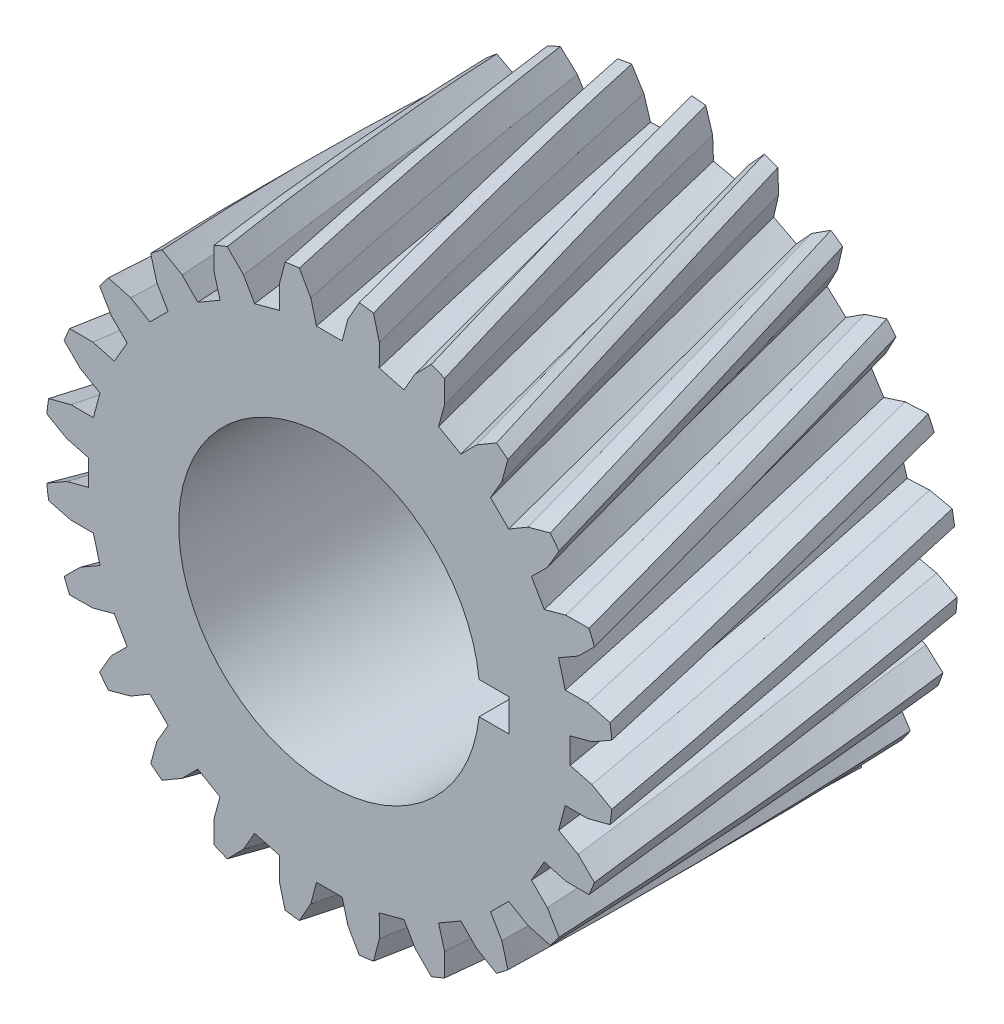
SolidWorks part; units mm, degrees
ref_plane "Front Plane" through (0, 0, 0) normal (0, 0, 1) x (1, 0, 0)
ref_plane "Top Plane" through (0, 0, 0) normal (0, 1, 0) x (1, 0, 0)
ref_plane "Right Plane" through (0, 0, 0) normal (1, 0, 0) x (0, 0, -1)
sketch "Sketch1" plane through (0, 0, 0) normal (0, 0, 1) x (1, 0, 0)
  circle A0 centre (0, 0) radius 13.2
  dimension "D1" = 26.4
extrude "Boss-Extrude1" add sketch "Sketch1" along normal blind 16
sketch "Sketch3" plane through (0, 0, 16) normal (0, 0, 1) x (1, 0, 0)
  circle A0 centre (0, 0) radius 13.2
curve "Helix/Spiral1" pitch 330 height 16.5 turns 0.05
sketch "Sketch4" plane through (0, 0, 16) normal (0, 0, 1) x (1, 0, 0)
  line L0 (0, 13.2) -> (0, 11.1888) construction
  line L1 (-0.596, 11.1888) -> (0.596, 11.1888)
  line L2 (0.596, 11.1888) -> (0.8611, 12.1944)
  line L3 (-0.596, 11.1888) -> (-0.8611, 12.1944)
  line L4 (0.8611, 12.1944) -> (1.5138, 13.3405)
  line L5 (-0.8611, 12.1944) -> (-1.5138, 13.3405)
  line L6 (1.5138, 13.3405) -> (-1.5138, 13.3405)
  circle A0 centre (0, 0) radius 13.2 construction
  spline S0 degree 3 poles (0, 13.2) (-0.4608, 13.2) (-1.3823, 13.1517) (-2.7494, 12.9352) (-3.6408, 12.6963) (-4.079, 12.5539) knots 0 0 0 0 0.333333 0.666667 1 1 1 1 construction
  dimension "D1" = 2.1518
  dimension "D2" = 59.317
  dimension "D3" = 1.0056
  dimension "D4" = 1.1461
  dimension "D5" = 1.192
sweep "Cut-Sweep1" cut profiles "Sketch4" path "Helix/Spiral1"
pattern_circular "CirPattern1" count 24 over 360 about axis through (0, 0, 0) along (0, 0, 1) of "Cut-Sweep1"
sketch "Sketch5" plane through (0, 0, 0) normal (0, 0, -1) x (-1, 0, 0)
  circle A0 centre (0, 0) radius 8.875
  dimension "D1" = 17.75
extrude "Boss-Extrude2" add sketch "Sketch5" along normal blind 0.2
sketch "Sketch6" plane through (0, 0, -0.2) normal (0, 0, -1) x (-1, 0, 0)
  circle A0 centre (0, 0) radius 7
  dimension "D1" = 14
extrude "Cut-Extrude1" cut sketch "Sketch6" against normal blind 39.2
sketch "Sketch7" plane through (0, 0, -0.2) normal (0, 0, -1) x (-1, 0, 0)
  line L1 (-6.9378, 0.75) -> (-8.3378, 0.75)
  line L3 (-6.9378, -0.75) -> (-8.3378, -0.75)
  line L4 (-8.3378, 0.75) -> (-8.3378, -0.75)
  line L6 (-7, 0) -> (-6.9378, -0.75)
  line L7 (-7, 0) -> (-6.9378, 0.75)
  circle A2 centre (0, 0) radius 7 construction
  point P0 (0, 0)
  point P3 (-8.3378, 0)
  dimension "D1" = 1.5
  dimension "D2" = 1.4
  dimension "D3" = 6.9378
extrude "Cut-Extrude2" cut sketch "Sketch7" against normal blind 39.2
